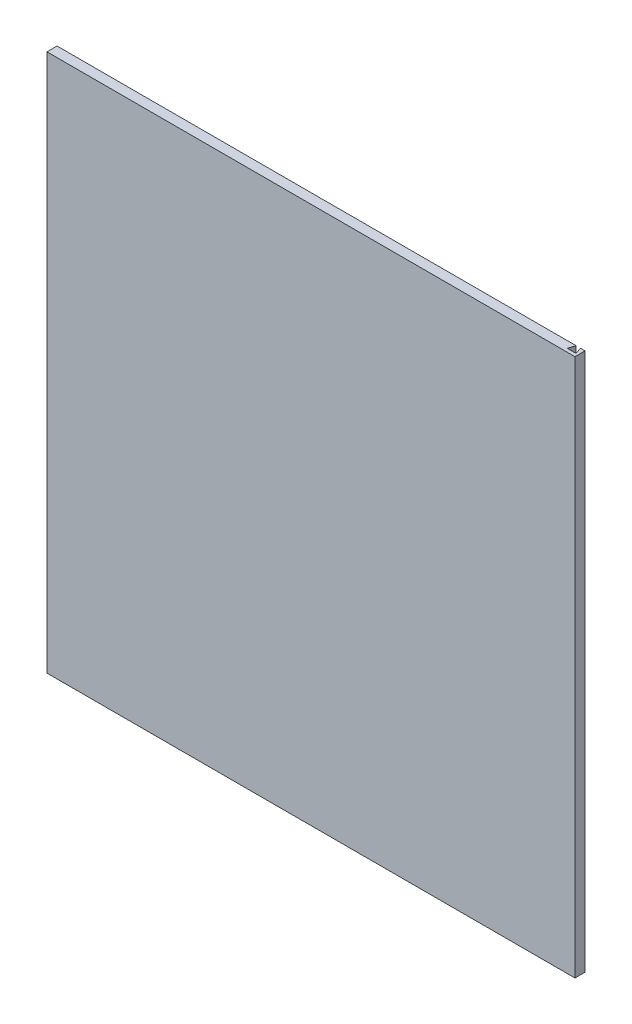
SolidWorks part; units mm, degrees
ref_plane "Front Plane" through (0, 0, 0) normal (0, 0, 1) x (1, 0, 0)
ref_plane "Top Plane" through (0, 0, 0) normal (0, 1, 0) x (1, 0, 0)
ref_plane "Right Plane" through (0, 0, 0) normal (1, 0, 0) x (0, 0, -1)
sketch "Sketch1" plane through (0, 0, 0) normal (0, 0, 1) x (1, 0, 0)
  line L1 (0, 0) -> (78.5, 0)
  line L2 (0, 0) -> (0, 80)
  line L3 (0, 80) -> (78.5, 80)
  line L4 (78.5, 0) -> (78.5, 80)
  dimension "D1" = 80
  dimension "D2" = 78.5
extrude "Boss-Extrude1" add sketch "Sketch1" along normal blind 1.5
sketch "Sketch2" plane through (0, 80, 0) normal (0, 1, 0) x (1, 0, 0)
  line L7 (78.5, -0.75) -> (73.8511, -0.75) construction
  line L8 (78.5, -1.5) -> (78.5, 0) construction
  line L9 (78.15, -1) -> (77.825, 0)
  line L10 (76.85, -1) -> (78.15, -1)
  line L11 (76.85, -1) -> (77.175, 0)
  line L12 (77.825, 0) -> (77.175, 0)
extrude "Cut-Extrude1" cut sketch "Sketch2" against normal up to surface (80 mm away) up to face at (39.25, 0, 0.75)
